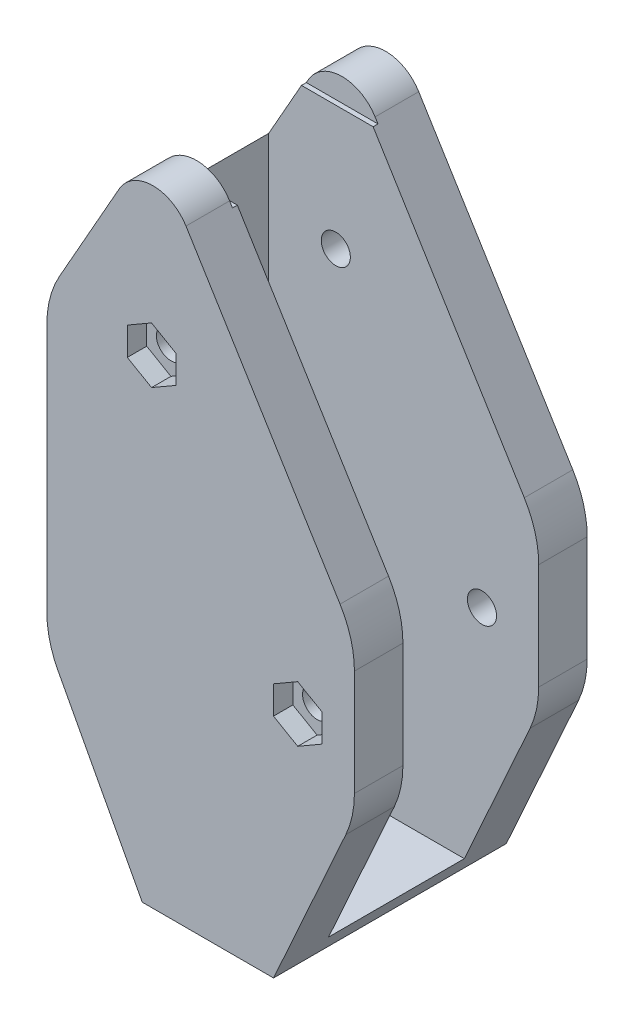
SolidWorks part; units mm, degrees
ref_plane "前视基准面" through (0, 0, 0) normal (0, 0, 1) x (1, 0, 0)
ref_plane "上视基准面" through (0, 0, 0) normal (0, 1, 0) x (1, 0, 0)
ref_plane "右视基准面" through (0, 0, 0) normal (1, 0, 0) x (0, 0, -1)
sketch "草图1" plane through (0, 0, 0) normal (0, 0, 1) x (1, 0, 0)
  line L8 (-29.8155, -4.2167) -> (49970.1845, -4.2167) construction
  line L9 (-29.8155, -28.7167) -> (49970.1845, -28.7167) construction
  line L10 (-8.8963, -4.2167) -> (26190.399, -42590.5634) construction
  line L20 (-8.8963, -35.0463) -> (-8.8963, 49964.9537) construction
  line L21 (-29.8155, -35.0463) -> (12.023, -35.0463)
  line L22 (-29.8155, -35.0463) -> (-29.8155, 26.613)
  line L23 (-29.8155, 26.613) -> (12.023, 26.613)
  line L24 (12.023, -35.0463) -> (12.023, 26.613)
  circle A0 centre (-8.8963, -4.2167) radius 1.5
  circle A1 centre (6.1762, -28.7167) radius 1.5
  point P5 (-29.8155, -4.2167)
  point P9 (-8.8963, -35.0463)
  dimension "D1" = 24.5
  dimension "D2" = 3
  dimension "D6" = 121.6
  dimension "D3" = 20.9193
  dimension "D7" = 3
  dimension "D4" = 61.6593
  dimension "D5" = 41.8385
extrude "凸台-拉伸1" add sketch "草图1" along normal blind 24
shell "抽壳2" thickness 5 removed face at (-8.8963, -35.0463, 12) removed face at (12.023, -4.2167, 12) removed face at (-8.8963, 26.613, 12)
sketch "草图7" plane through (12.023, 0, 0) normal (1, 0, 0) x (0, 0, -1)
  line L1 (-19, 26.613) -> (-5, 26.613)
  line L2 (-19, 26.613) -> (-19, -35.0463)
  line L3 (-19, -35.0463) -> (-5, -35.0463)
  line L4 (-5, 26.613) -> (-5, -35.0463)
  dimension "D1" = 61.6593
  dimension "D2" = 14
extrude "切除-拉伸2" cut sketch "草图7" against normal blind 38
sketch "草图11" plane through (-29.8155, 0, 0) normal (-1, 0, 0) x (0, 0, 1)
  line L1 (19, 26.613) -> (5, 26.613)
  line L2 (19, 26.613) -> (19, -35.0463)
  line L3 (19, -35.0463) -> (5, -35.0463)
  line L4 (5, 26.613) -> (5, -35.0463)
  dimension "D1" = 61.6593
  dimension "D2" = 14
extrude "凸台-拉伸2" add sketch "草图11" against normal blind 14
sketch "草图12" plane through (0, 0, 24) normal (0, 0, 1) x (1, 0, 0)
  line L1 (-29.8155, 26.613) -> (-19.6941, 26.613)
  line L2 (-29.8155, 26.613) -> (-29.8155, -35.0463)
  line L3 (-29.8155, -35.0463) -> (-19.6941, -35.0463)
  line L4 (-19.6941, 26.613) -> (-19.6941, -35.0463)
  line L5 (-29.8155, -35.0463) -> (12.023, -35.0463) construction
  dimension "D1" = 61.6593
  dimension "D2" = 10.1214
extrude "切除-拉伸3" cut sketch "草图12" against normal through all
sketch "草图17" plane through (0, 0, 24) normal (0, 0, 1) x (1, 0, 0)
  line L0 (-8.8963, -4.2167) -> (-8.8963, 49995.7833) construction
  line L1 (-8.8963, 26.613) -> (-8.8963, 14.8678)
  line L2 (12.023, 26.613) -> (-19.6941, 26.613) construction
  line L3 (-8.8963, 14.8678) -> (12.023, -19.136)
  line L4 (12.023, -35.0463) -> (12.023, 26.613) construction
  line L5 (12.023, -19.136) -> (12.023, 26.613)
  line L6 (12.023, 26.613) -> (-8.8963, 26.613)
  line L7 (-8.8963, -4.2167) -> (26190.399, -42590.5634) construction
  dimension "D1" = 10
extrude "切除-拉伸5" cut sketch "草图17" against normal through all
sketch "草图18" plane through (-19.6941, 0, 0) normal (-1, 0, 0) x (0, 0, 1)
  line L0 (0, 26.613) -> (24, 26.613) construction
  line L1 (4.5, 26.613) -> (19.5, 26.613)
  line L2 (4.5, 26.613) -> (4.5, 8.613)
  line L3 (4.5, 8.613) -> (19.5, 8.613)
  line L4 (19.5, 26.613) -> (19.5, 8.613)
  line L5 (0, -35.0463) -> (0, 26.613) construction
  line L6 (24, -35.0463) -> (24, 26.613) construction
  dimension "D1" = 18
  dimension "D2" = 15
  dimension "D3" = 4.5
  dimension "D4" = 4.5
extrude "切除-拉伸6" cut sketch "草图18" against normal through all
sketch "草图20" plane through (0, 0, 24) normal (0, 0, 1) x (1, 0, 0)
  line L0 (-19.6941, -35.0463) -> (-9.8535, -53.541)
  line L1 (-9.8535, -53.541) -> (3.6836, -53.541)
  line L2 (3.6836, -53.541) -> (12.023, -35.0463)
  line L3 (12.023, -35.0463) -> (-19.6941, -35.0463)
extrude "凸台-拉伸5" add sketch "草图20" against normal blind 24
sketch "草图22" plane through (0, -35.0463, 0) normal (0, 1, 0) x (1, 0, 0)
  line L1 (-15.8155, -5) -> (12.023, -5)
  line L2 (-15.8155, -5) -> (-15.8155, -19)
  line L3 (-15.8155, -19) -> (12.023, -19)
  line L4 (12.023, -5) -> (12.023, -19)
  dimension "D1" = 14
  dimension "D2" = 27.8385
extrude "切除-拉伸8" cut sketch "草图22" against normal blind 17
ref_plane "基准面4" through (-29.8818, -15.8995, 0) normal (0.8828, 0.4697, 0) x (0, 0, -1)
sketch "草图23" plane through (-29.8818, -15.8995, 0) normal (0.8828, 0.4697, 0) x (0, 0, -1)
  line L5 (-19.4003, -29.5799) -> (-4.4092, -29.5799)
  line L6 (-19.4003, -29.5799) -> (-19.4003, -41.3133)
  line L7 (-19.4003, -41.3133) -> (-4.4092, -41.3133)
  line L8 (-4.4092, -29.5799) -> (-4.4092, -41.3133)
  dimension "D1" = 11.7334
  dimension "D2" = 14.9912
extrude "凸台-拉伸8" add sketch "草图23" along normal blind 2
fillet "圆角3" radius 4 1 edges at (-14.2217, -41.0735, 12)
sketch "草图24" plane through (0, 0, 0) normal (0, 0, -1) x (-1, 0, 0)
  line L0 (8.8963, 14.8678) -> (19.6941, -4.2167)
  line L1 (19.6941, -35.0463) -> (19.6941, 26.613) construction
  line L2 (19.6941, -4.2167) -> (19.6941, 26.613)
  line L3 (19.6941, 26.613) -> (8.8963, 26.613)
  line L4 (8.8963, 26.613) -> (8.8963, 14.8678)
extrude "切除-拉伸9" cut sketch "草图24" against normal through all
fillet "圆角4" radius 4 2 edges at (-8.8963, 14.8678, 21.75) (-8.8963, 14.8678, 2.25)
fillet "圆角5" radius 10 6 edges at (-19.6941, -35.0463, 12) (-19.6941, -4.2167, 12) (12.023, -35.0463, 21.5) (12.023, -35.0463, 2.5) (12.023, -19.136, 2.5) (12.023, -19.136, 21.5)
sketch "草图25" plane through (0, 0, 24) normal (0, 0, 1) x (1, 0, 0)
  line L0 (-19.6941, -32.5515) -> (-19.6941, -6.8495) construction
  line L1 (-8.8963, -7.1034) -> (-6.3963, -5.6601)
  line L2 (-6.3963, -5.6601) -> (-6.3963, -2.7733)
  line L3 (-6.3963, -2.7733) -> (-8.8963, -1.3299)
  line L4 (-8.8963, -1.3299) -> (-11.3963, -2.7733)
  line L5 (-11.3963, -2.7733) -> (-11.3963, -5.6601)
  line L6 (-11.3963, -5.6601) -> (-8.8963, -7.1034)
  line L7 (6.1762, -25.8299) -> (3.6762, -27.2733)
  line L8 (3.6762, -27.2733) -> (3.6762, -30.1601)
  line L9 (3.6762, -30.1601) -> (6.1762, -31.6034)
  line L10 (6.1762, -31.6034) -> (8.6762, -30.1601)
  line L11 (8.6762, -30.1601) -> (8.6762, -27.2733)
  line L12 (8.6762, -27.2733) -> (6.1762, -25.8299)
  circle A0 centre (-8.8963, -4.2167) radius 2.5 construction
  circle A1 centre (6.1762, -28.7167) radius 2.5 construction
  dimension "D1" = 5
  dimension "D2" = 5
extrude "切除-拉伸10" cut sketch "草图25" against normal blind 2
sketch "草图26" plane through (0, 0, 0) normal (0, 0, -1) x (-1, 0, 0)
  circle A0 centre (8.8963, -4.2167) radius 2.5
  circle A1 centre (-6.1762, -28.7167) radius 2.5
  dimension "D1" = 5
  dimension "D2" = 5
extrude "切除-拉伸11" cut sketch "草图26" against normal blind 1
